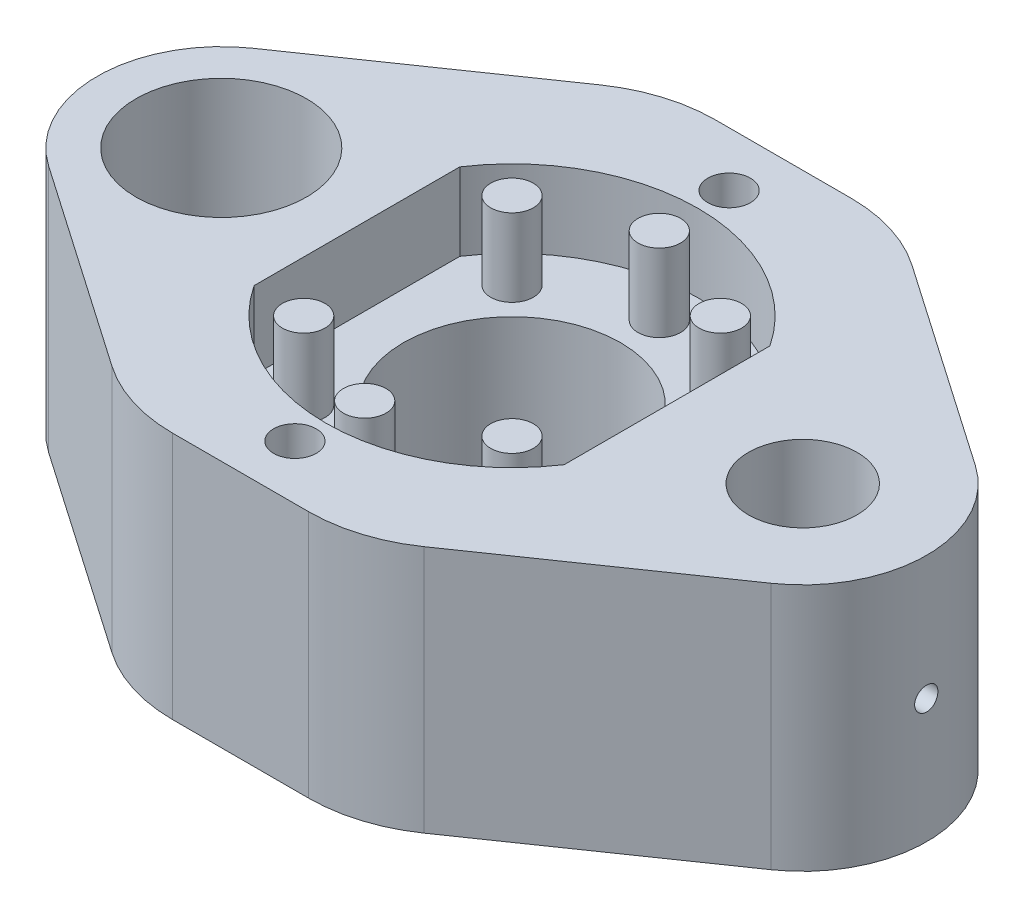
SolidWorks part; units mm, degrees
ref_plane "Front Plane" through (0, 0, 0) normal (0, 0, 1) x (1, 0, 0)
ref_plane "Top Plane" through (0, 0, 0) normal (0, 1, 0) x (1, 0, 0)
ref_plane "Right Plane" through (0, 0, 0) normal (1, 0, 0) x (0, 0, -1)
sketch "Sketch1" plane through (0, 0, 0) normal (0, 1, 0) x (1, 0, 0)
  line L0 (-20, 13.2665) -> (-20, -13.2665)
  line L1 (20, 13.2665) -> (20, -13.2665)
  line L2 (-15, -35) -> (15, -35)
  line L3 (-15, -35) -> (-46.5969, -13.1623)
  line L4 (0, 105.5868) -> (0, -105.5868) construction
  line L5 (15, -35) -> (46.5969, -13.1623)
  line L6 (-86.2788, 0) -> (86.2788, 0) construction
  line L7 (-15, 35) -> (15, 35)
  line L8 (15, 35) -> (46.5969, 13.1623)
  line L9 (-15, 35) -> (-46.5969, 13.1623)
  circle A0 centre (0, 0) radius 14
  arc A1 (-20, -13.2665) -> (20, -13.2665) centre (0, 0) ccw
  arc A2 (20, 13.2665) -> (-20, 13.2665) centre (0, 0) ccw
  arc A3 (-46.5969, 13.1623) -> (-46.5969, -13.1623) centre (-37.5, 0) ccw
  circle A4 centre (-37.5, 0) radius 11
  circle A5 centre (37.5, 0) radius 7
  arc A6 (46.5969, 13.1623) -> (46.5969, -13.1623) centre (37.5, 0) cw
  point P13 (0, -35)
  point P16 (0, 0)
  point P24 (0, 0)
  dimension "D1" = 28
  dimension "D2" = 48
  dimension "D4" = 22
  dimension "D5" = 32
  dimension "D9" = 14
  dimension "D3" = 40
  dimension "D6" = 37.5
  dimension "D7" = 30
  dimension "D8" = 35
extrude "Extrude2" add sketch "Sketch1" along normal blind 32 contours A6 L8 L7 L9 A3 L3 L2 L5 A2 L1 A1 L0 A4 region at (-30.0715, 0, 23.0293)
extrude "Extrude3" add sketch "Sketch" along normal offset from surface (22 mm away) 10 contours L1 A2 L0 A1 A0 region at (0, 0, -23.3752) up to face at (0, 32, 0)
sketch "Sketch" plane through (0, 0, 0) normal (0, 1, 0) x (1, 0, 0) same geometry as "Sketch1"
fillet "Fillet1" radius 20 4 edges at (-15, 16, -35) (15, 16, -35) (15, 16, 35) (-15, 16, 35)
sketch "Sketch5" plane through (0, 22, 0) normal (0, 1, 0) x (1, 0, 0)
  circle A0 centre (13.435, 13.435) radius 2.75
  circle A1 centre (13.435, 13.435) radius 2.75 construction
  dimension "D1" = 5.5
extrude "Extrude5" add sketch "Sketch5" along normal up to surface (10 mm away) up to face at (0, 32, 0)
pattern_circular "CirPattern1" count 3 every 45 about axis through (0, 22, 0) along (0, 1, 0) of "Extrude5"
mirror "Mirror1" about plane through (0, 0, 0) normal (0, 0, 1) of "Extrude5", "CirPattern1"
sketch3d "3DSketch3"
  circle A0 centre (37.5, 16, 0) radius 8
  circle A1 centre (37.5, 16, 0) radius 1.5
  circle A2 centre (37.5, 32, 0) radius 7 construction
  point P3 (37.5, 39, 0)
  point P5 (39, 16, 0)
  point P7 (37.5, 24, 0)
  dimension "D1" = 16
  dimension "D2" = 16
  dimension "D3" = 3
extrude "Extrude10" cut sketch "3DSketch3" along direction (0, 1, 0) on the side against the normal mid plane 3 contours A0
extrude "Extrude11" cut sketch "Sketch" along direction (1, 0, 0) on the side of the normal through all contours A1
sketch3d "Sketch" same geometry as "3DSketch3"
hole_wizard "M5 Clearance Hole1" positions "Sketch6" profile "Sketch7" hole size "M5" standard "ISO" end condition through all
sketch "Sketch6" plane through (0, 32, 0) normal (0, 1, 0) x (1, 0, 0)
  point P0 (0, 28)
  point P3 (0, -28)
sketch "Sketch7" plane through (0, 32, -28) normal (1, 0, 0) x (0, 0, 1)
  line L0 (0, 0) -> (0, 32)
  line L1 (0, 32) -> (2.75, 32)
  line L2 (2.75, 32) -> (2.75, 0)
  line L5 (2.75, 0) -> (0, 0)
  line L11 (0, -6.35) -> (0, 107.95) construction
  dimension "Thru Hole Dia." = 5.5
  dimension "Thru Hole Depth" = 32
